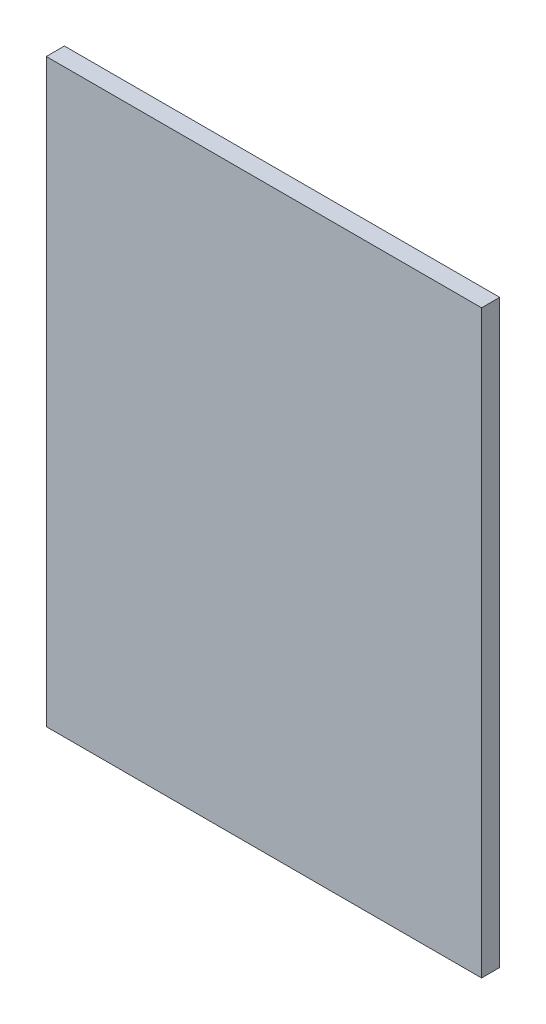
SolidWorks part; units mm, degrees
ref_plane "Front Plane" through (0, 0, 0) normal (0, 0, 1) x (1, 0, 0)
ref_plane "Top Plane" through (0, 0, 0) normal (0, 1, 0) x (1, 0, 0)
ref_plane "Right Plane" through (0, 0, 0) normal (1, 0, 0) x (0, 0, -1)
sketch "Sketch1" plane through (0, 0, 0) normal (0, 0, 1) x (1, 0, 0)
  line L1 (-30, 40) -> (30, 40)
  line L2 (-30, 40) -> (-30, -40)
  line L3 (-30, -40) -> (30, -40)
  line L4 (30, 40) -> (30, -40)
  line L5 (-30, 40) -> (30, -40) construction
  line L6 (-30, -40) -> (30, 40) construction
  point P0 (0, 0)
  dimension "D1" = 60
  dimension "D2" = 80
extrude "Boss-Extrude1" add sketch "Sketch1" along normal blind 2.5
